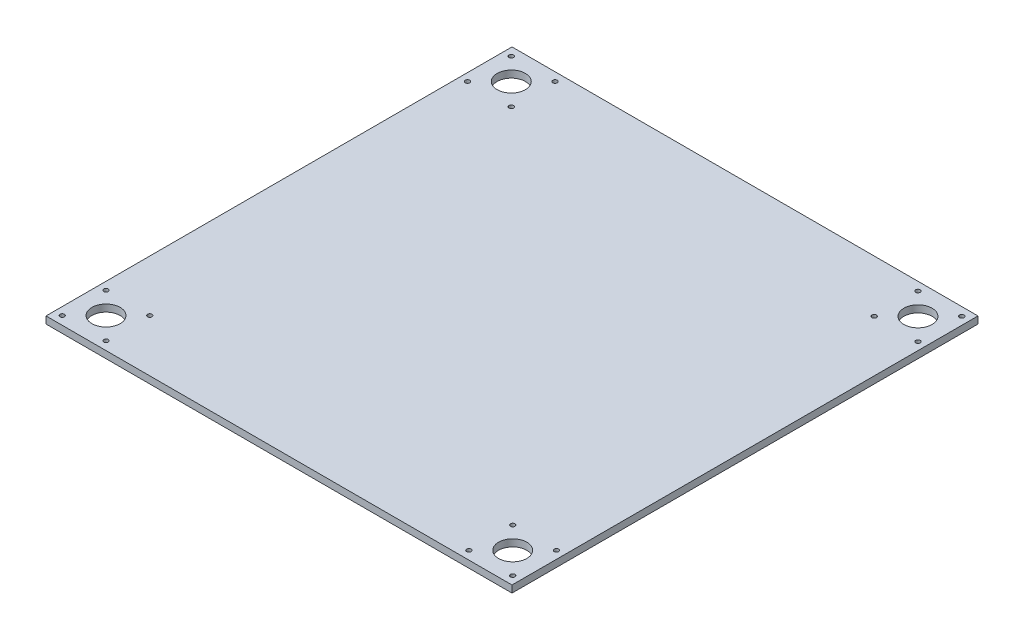
SolidWorks part; units mm, degrees
ref_plane "前视基准面" through (0, 0, 0) normal (0, 0, 1) x (1, 0, 0)
ref_plane "上视基准面" through (0, 0, 0) normal (0, 1, 0) x (1, 0, 0)
ref_plane "右视基准面" through (0, 0, 0) normal (1, 0, 0) x (0, 0, -1)
other "Configuration Table"
sketch "草图1" plane through (0, 0, 0) normal (0, 1, 0) x (1, 0, 0)
  line L1 (165, -165) -> (-165, -165)
  line L2 (165, -165) -> (165, 165)
  line L3 (165, 165) -> (-165, 165)
  line L4 (-165, -165) -> (-165, 165)
  line L5 (165, -165) -> (-165, 165) construction
  line L6 (165, 165) -> (-165, -165) construction
  point P0 (0, 0)
  dimension "D1" = 330
  dimension "D2" = 330
extrude "凸台-拉伸1" add sketch "草图1" along normal blind 5
sketch "草图2" plane through (0, 5, 0) normal (0, 1, 0) x (1, 0, 0)
  circle A0 centre (-159.5, 159) radius 1.6
  circle A1 centre (-128.5, 159) radius 1.6
  circle A2 centre (-159.5, 128) radius 1.6022
  circle A3 centre (-128.5, 128) radius 1.6
  circle A4 centre (128.5, 159) radius 1.6
  circle A5 centre (159.5, 159) radius 1.6
  circle A6 centre (128.5, 128) radius 1.6
  circle A7 centre (159.5, 128) radius 1.6
  circle A8 centre (128.5, -128) radius 1.6
  circle A9 centre (159.5, -128) radius 1.6
  circle A10 centre (159.5, -159) radius 1.6
  circle A11 centre (128.5, -159) radius 1.6
  circle A12 centre (-128.5, -159) radius 1.6
  circle A13 centre (-159.5, -159) radius 1.6
  circle A14 centre (-159.5, -128) radius 1.6
  circle A15 centre (-128.5, -128) radius 1.6
extrude "切除-拉伸1" cut sketch "草图2" against normal through all
sketch "草图3" plane through (0, 5, 0) normal (0, 1, 0) x (1, 0, 0)
  line L0 (-110, 60) -> (-110, 40)
  line L1 (110, -110) -> (-110, -110) construction
  line L2 (110, -110) -> (110, 110) construction
  line L3 (110, 110) -> (-110, 110) construction
  line L4 (-110, -110) -> (-110, 110) construction
  line L5 (110, -110) -> (-110, 110) construction
  line L6 (110, 110) -> (-110, -110) construction
  line L7 (-110, 110) -> (110, 110)
  line L8 (-110, 110) -> (-110, 90)
  line L9 (-110, 90) -> (110, 90)
  line L10 (110, 110) -> (110, 90)
  line L11 (-110, 60) -> (110, 60)
  line L12 (110, 60) -> (110, 40)
  line L13 (-110, 40) -> (110, 40)
  line L14 (-110, 10) -> (-110, -10)
  line L15 (-110, 10) -> (110, 10)
  line L16 (110, 10) -> (110, -10)
  line L17 (-110, -10) -> (110, -10)
  line L18 (-110, -40) -> (-110, -60)
  line L19 (-110, -40) -> (110, -40)
  line L20 (110, -40) -> (110, -60)
  line L21 (-110, -60) -> (110, -60)
  line L22 (-110, -90) -> (-110, -110)
  line L23 (-110, -90) -> (110, -90)
  line L24 (110, -90) -> (110, -110)
  line L25 (-110, -110) -> (110, -110)
  point P0 (0, 0)
  dimension "D1" = 220
  dimension "D2" = 220
  dimension "D3" = 20
  dimension "D4" = 5
extrude "切除-拉伸2" cut sketch "草图3" against normal through all contours L10 L7 L8 L9 | L0 L13 L12 L11 | L14 L17 L16 L15 | L18 L21 L20 L19 | L22 L25 L24 L23 | L8 L7 L10 L9 | L0 L13 L12 L11 region at (0, 5, -50) region at (0, 5, -100) region at (0, 5, 0) region at (0, 5, 50) region at (0, 5, 100)
sketch "草图8" plane through (0, 5, 0) normal (0, 1, 0) x (1, 0, 0)
  line L0 (120, 0) -> (-120, 0)
  line L1 (0, -120) -> (0, 120)
  line L2 (-224.7688, 66.7151) -> (-262.2303, -15.7843) construction
  line L3 (-262.2303, -15.7843) -> (-279.9088, 51.9831) construction
  line L4 (-279.9088, 51.9831) -> (-224.7688, 66.7151) construction
  point P4 (0, 0)
  point P8 (0, 0)
sketch "草图9" plane through (0, 5, 0) normal (0, 1, 0) x (1, 0, 0)
  line L1 (-117.6798, 117.0824) -> (121.8613, 117.0824)
  line L2 (-117.6798, 117.0824) -> (-117.6798, -116.4851)
  line L3 (-117.6798, -116.4851) -> (121.8613, -116.4851)
  line L4 (121.8613, 117.0824) -> (121.8613, -116.4851)
extrude "凸台-拉伸2" add sketch "草图9" against normal blind 5
sketch "草图10" plane through (0, 5, 0) normal (0, 1, 0) x (1, 0, 0)
  line L0 (-159.5, 159) -> (-128.5, 128) construction
  line L1 (0, -120) -> (0, 120) construction
  line L2 (0, -120) -> (0, 120)
  line L3 (120, 0) -> (-120, 0) construction
  line L4 (120, 0) -> (-120, 0)
  circle A0 centre (-144, 143.5) radius 10
  circle A1 centre (144, 143.5) radius 10
  circle A2 centre (144, -143.5) radius 10
  circle A3 centre (-144, -143.5) radius 10
  dimension "D1" = 20
extrude "切除-拉伸5" cut sketch "草图10" against normal blind 10 contours A0 L0 | L0 A0 | A1 | A2 | A3 region at (-140.9989, 5, -146.5011) region at (-147.0011, 5, -140.4989) region at (144, 5, -143.5) region at (144, 5, 143.5) region at (-144, 5, 143.5)
